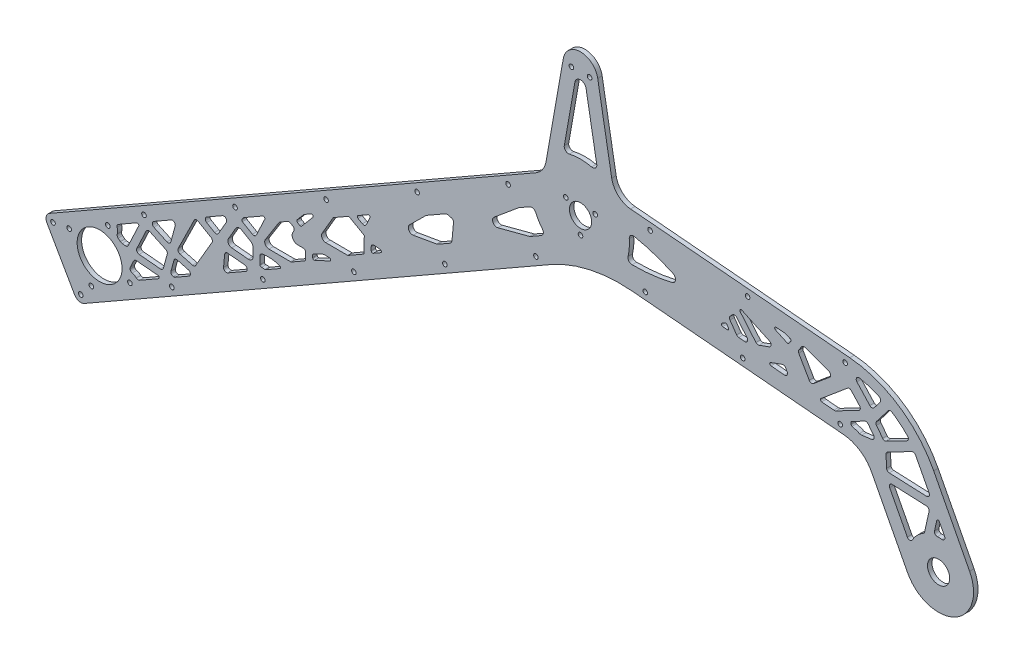
SolidWorks part; units mm, degrees
material "6061-T6 (SS)"
ref_plane "Front Plane" through (0, 0, 0) normal (0, 0, 1) x (1, 0, 0)
ref_plane "Top Plane" through (0, 0, 0) normal (0, 1, 0) x (1, 0, 0)
ref_plane "Right Plane" through (0, 0, 0) normal (1, 0, 0) x (0, 0, -1)
sketch "Reference Sketch" plane through (0, 0, 0) normal (0, 0, 1) x (1, 0, 0)
  line L0 (-343.92, -196.825) -> (0, 0) construction
  line L1 (-243.92, 103.175) -> (356.08, 103.175) construction
  line L2 (-243.92, 103.175) -> (-243.92, 0) construction
  line L3 (-243.92, 0) -> (356.08, 0) construction
  line L4 (356.08, 103.175) -> (356.08, 0) construction
  line L5 (0, 0) -> (256.08, -92.7116) construction
  line L6 (256.08, -92.7116) -> (56.08, -196.825) construction
  line L7 (256.08, -92.7116) -> (456.08, -196.825) construction
  line L8 (-343.92, -196.825) -> (56.08, -196.825) construction
  line L9 (56.08, -196.825) -> (456.08, -196.825) construction
  circle A1 centre (-343.92, -196.825) radius 100 construction
  circle A2 centre (56.08, -196.825) radius 100 construction
  circle A3 centre (456.08, -196.825) radius 100 construction
  circle A4 centre (-343.92, -196.825) radius 16.05 construction
  circle A5 centre (-343.92, -196.825) radius 28.55 construction
  circle A6 centre (-343.92, -196.825) radius 38.55 construction
  circle A7 centre (-343.92, -196.825) radius 33.55 construction
  point P13 (-343.92, -296.825)
  point P14 (556.08, -196.825)
  point P17 (-443.92, -196.825)
  dimension "D3" = 32.1
  dimension "D5" = 200
  dimension "D9" = 57.1
  dimension "D10" = 10
  dimension "D11" = 5
  dimension "D1" = 600
  dimension "D2" = 103.175
  dimension "D4" = 243.92
  dimension "D6" = 125
  dimension "D7" = 400
  dimension "D8" = 1000
sketch "Sketch2" plane through (0, 0, 0) normal (0, 0, 1) x (1, 0, 0)
  line L0 (-379.7168, -188.5069) -> (-32.0065, 10.4873)
  line L1 (-354.8814, -231.9028) -> (-21.5627, -41.1449)
  line L2 (-343.92, -196.825) -> (0, 0) construction
  line L3 (-184.3777, -76.7146) -> (-159.5423, -120.1104) construction
  line L4 (-24.685, 20.9013) -> (-12.3101, 91.0831)
  line L5 (12.3101, 91.0831) -> (22.322, 34.3028)
  line L6 (0, 98.4125) -> (0, 112.7) construction
  line L7 (-5.4848, 79.4125) -> (5.4848, 79.4125) construction
  line L8 (5.4848, 79.4125) -> (10.9697, 88.9125) construction
  line L9 (10.9697, 88.9125) -> (5.4848, 98.4125) construction
  line L10 (5.4848, 98.4125) -> (-5.4848, 98.4125) construction
  line L11 (-5.4848, 98.4125) -> (-10.9697, 88.9125) construction
  line L12 (-10.9697, 88.9125) -> (-5.4848, 79.4125) construction
  line L13 (-243.92, 103.175) -> (356.08, 103.175) construction
  line L14 (0, 88.9125) -> (0, 0) construction
  line L15 (35.7868, 21.9646) -> (192.5861, 8.2464)
  line L16 (252.5753, -31.8371) -> (278.2553, -81.1679)
  line L17 (233.9047, -104.2553) -> (208.2247, -54.9245)
  line L18 (36.8237, -28.3172) -> (188.2284, -41.5633)
  line L19 (0, 0) -> (192.5861, -16.8491) construction
  line L21 (-365.6311, -190.9191) -> (-338.0141, -175.1139) construction
  line L22 (-381.5729, -195.33) -> (-361.7045, -230.0467)
  line L23 (256.08, -92.7116) -> (56.08, -196.825) construction
  line L25 (-243.92, 0) -> (356.08, 0) construction
  circle A0 centre (0, 0) radius 7.9375
  circle A1 centre (-343.92, -196.825) radius 16.05
  arc A3 (-12.3101, 91.0831) -> (12.3101, 91.0831) centre (0, 88.9125) cw
  circle A4 centre (0, 88.9125) radius 6.5 construction
  circle A5 centre (-6.5, 88.9125) radius 1.65
  circle A6 centre (6.5, 88.9125) radius 1.65
  circle A7 centre (0, 88.9125) radius 9.5 construction
  arc A8 (252.5753, -31.8371) -> (192.5861, 8.2464) centre (186.0495, -66.4682) ccw
  circle A9 centre (256.08, -92.7116) radius 7.9375
  arc A10 (278.2553, -81.1679) -> (233.9047, -104.2553) centre (256.08, -92.7116) cw
  arc A11 (-21.5627, -41.1449) -> (36.8237, -28.3172) centre (28.1082, -127.9366) cw
  arc A12 (188.2284, -41.5633) -> (208.2247, -54.9245) centre (186.0495, -66.4682) cw
  arc A13 (22.322, 34.3028) -> (35.7868, 21.9646) centre (37.0941, 36.9075) ccw
  arc A14 (-32.0065, 10.4873) -> (-24.685, 20.9013) centre (-39.4572, 23.506) ccw
  circle A17 centre (-343.92, -196.825) radius 22.5 construction
  circle A18 centre (-365.6311, -190.9191) radius 1.65
  circle A19 centre (-338.0141, -175.1139) radius 1.65
  circle A20 centre (-322.2089, -202.7309) radius 1.65
  circle A21 centre (-349.8259, -218.5361) radius 1.65
  arc A27 (-379.7168, -188.5069) -> (-381.5729, -195.33) centre (-377.2333, -192.8465) ccw
  arc A28 (-361.7045, -230.0467) -> (-354.8814, -231.9028) centre (-357.3649, -227.5632) ccw
  circle A29 centre (-343.92, -196.825) radius 33.55 construction
  circle A32 centre (-343.92, -196.825) radius 38.55 construction
  point P16 (-171.96, -98.4125)
  point P64 (-343.92, -196.825)
  dimension "D1" = 15.875
  dimension "D2" = 32.1
  dimension "D3" = 45
  dimension "D5" = 13
  dimension "D6" = 3.3
  dimension "D7" = 6
  dimension "D12" = 50
  dimension "D14" = 100
  dimension "D16" = 15
  dimension "D17" = 5
  dimension "D18" = 25
  dimension "D19" = 3.3
  dimension "D15" = 4
  dimension "D4" = 50
  dimension "D8" = 19
  dimension "D9" = 14.2875
  dimension "D10" = 9.525
  dimension "D11" = 10
  dimension "D13" = 50
extrude "Base" add sketch "Sketch2" along normal blind 3.175
sketch "Sketch3" plane through (0, 0, 3.175) normal (0, 0, 1) x (1, 0, 0)
  line L0 (-343.92, -196.825) -> (0, 0) construction
  line L5 (0, 0) -> (197.3986, -17.2701) construction
  line L6 (192.5861, 8.2464) -> (35.7868, 21.9646) construction
  line L9 (36.8237, -28.3172) -> (188.2284, -41.5633) construction
  line L10 (-31.8958, -41.2976) -> (0, 0) construction
  line L11 (0, 0) -> (46.2693, -24.1244) construction
  circle A0 centre (-357.3649, -227.5632) radius 1.65
  circle A1 centre (-343.92, -196.825) radius 33.55 construction
  arc A2 (-361.7045, -230.0467) -> (-354.8814, -231.9028) centre (-357.3649, -227.5632) ccw construction
  circle A3 centre (-292.2711, -190.3101) radius 1.65
  circle A4 centre (-227.1773, -153.057) radius 1.65
  circle A5 centre (-162.0835, -115.8038) radius 1.65
  circle A6 centre (-96.9897, -78.5507) radius 1.65
  circle A7 centre (-31.8958, -41.2976) radius 1.65
  circle A8 centre (-312.1394, -155.5934) radius 1.65
  circle A9 centre (-377.2333, -192.8465) radius 1.65
  circle A10 centre (-247.0456, -118.3403) radius 1.65
  circle A11 centre (-181.9518, -81.0871) radius 1.65
  circle A12 centre (-116.858, -43.834) radius 1.65
  circle A13 centre (-51.7642, -6.5809) radius 1.65
  circle A14 centre (46.2693, -24.1244) radius 1.65
  circle A15 centre (116.0029, -30.2253) radius 1.65
  circle A16 centre (185.7366, -36.3262) radius 1.65
  circle A17 centre (189.2228, 3.5215) radius 1.65
  circle A18 centre (119.4892, 9.6224) radius 1.65
  circle A19 centre (49.7555, 15.7234) radius 1.65
  dimension "D1" = 3.3
  dimension "D2" = 6
  dimension "D3" = 5
  dimension "D5" = 3
  dimension "D4" = 75
  dimension "D6" = 70
extrude "Strut Holes" cut sketch "Sketch3" against normal through all
sketch "Sketch6" plane through (0, 0, 3.175) normal (0, 0, 1) x (1, 0, 0)
  line L0 (-315.2692, -197.7109) -> (-301.7593, -189.9792)
  line L1 (-354.8814, -231.9028) -> (-21.5627, -41.1449) construction
  line L2 (-289.845, -183.1607) -> (-279.9388, -177.4914)
  line L3 (-225.0683, -146.089) -> (-215.0659, -140.3647)
  line L4 (-202.4189, -105.5114) -> (-200.6862, -106.5205)
  line L5 (-330.4255, -170.6672) -> (-317.3783, -163.2003)
  line L6 (-32.0065, 10.4873) -> (-379.7168, -188.5069) construction
  line L7 (-315.9769, -164.4942) -> (-323.4022, -180.2613)
  line L8 (-325.3934, -181.4009) -> (-327.8261, -181.1787)
  line L9 (-302.165, -188.1154) -> (-317.5291, -186.7124)
  line L10 (-319.5204, -187.852) -> (-321.9207, -192.9489)
  line L11 (-295.5333, -171.6316) -> (-298.2962, -181.7883)
  line L12 (-300.4079, -183.2551) -> (-315.6625, -181.8621)
  line L13 (-317.2901, -179.0183) -> (-310.6415, -164.9005)
  line L14 (-307.9799, -163.9432) -> (-296.6111, -169.2972)
  line L15 (-280.4073, -173.8257) -> (-288.2923, -171.6808)
  line L16 (-290.7472, -173.0857) -> (-292.8686, -180.8843)
  line L17 (-292.7787, -149.122) -> (-305.2156, -156.2396)
  line L18 (-305.0743, -159.7848) -> (-295.766, -164.1685)
  line L19 (-292.984, -162.8841) -> (-289.8554, -151.3828)
  line L20 (-286.4122, -167.0105) -> (-277.4777, -169.4409)
  line L21 (-275.2245, -168.5176) -> (-263.487, -148.3649)
  line L22 (-264.2087, -145.6301) -> (-273.4911, -140.2238)
  line L23 (-276.2919, -141.0684) -> (-287.6814, -164.1971)
  line L24 (-267.3269, -134.556) -> (-255.9817, -128.0631)
  line L25 (-253.26, -130.8055) -> (-258.9575, -140.5878)
  line L26 (-261.6923, -141.3094) -> (-267.3401, -138.02)
  line L27 (-255.2613, -159.7424) -> (-254.4886, -151.2802)
  line L28 (-252.315, -149.4703) -> (-240.2297, -150.5739)
  line L29 (-292.2711, -190.3101) -> (-299.0066, -188.4038) construction
  line L30 (-252.2762, -161.6601) -> (-239.4181, -154.3014)
  line L31 (-246.5402, -131.1894) -> (-251.7948, -140.2114)
  line L32 (-249.4752, -144.7088) -> (-237.508, -145.8016)
  line L33 (-234.2352, -142.8254) -> (-234.2117, -136.6339)
  line L34 (-235.7018, -134.0302) -> (-242.4379, -130.1069)
  line L35 (-229.2226, -139.4963) -> (-229.2439, -145.1246)
  line L36 (-241.7536, -124.7193) -> (-234.6398, -128.8625)
  line L37 (-231.8238, -127.9864) -> (-225.7969, -115.1887)
  line L38 (-227.1983, -113.8948) -> (-240.4869, -121.4998)
  line L39 (-215.6688, -112.1749) -> (-225.38, -127.5855)
  line L40 (-222.8533, -132.1849) -> (-207.4544, -132.2434)
  line L41 (-206.4534, -131.9792) -> (-197.5057, -126.8584)
  line L42 (-196.4991, -125.1302) -> (-196.4845, -121.2849)
  line L43 (-198.4769, -119.2773) -> (-202.2607, -119.2629)
  line L44 (-205.6297, -113.1304) -> (-205.0269, -112.1739)
  line L45 (-205.7124, -109.3794) -> (-207.4618, -108.3605)
  line L46 (-209.4618, -108.3529) -> (-214.9702, -111.5053)
  line L47 (-223.2993, -137.1832) -> (-189.5978, -137.3112) construction
  line L48 (-199.4194, -106.3021) -> (-191.3609, -96.7721)
  line L49 (-192.6212, -95.2585) -> (-197.479, -98.0386)
  line L50 (-198.0128, -98.4831) -> (-202.6792, -104.0016)
  line L51 (-191.4798, -120.0542) -> (-191.4866, -121.8475)
  line L52 (-190.0674, -122.7592) -> (-179.2455, -117.7628)
  line L54 (-190.899, -119.1501) -> (-184.1308, -116.0253)
  line L55 (-183.2849, -115.8411) -> (-179.6609, -115.8549)
  line L56 (-166.4011, -107.9052) -> (-182.2049, -107.8452)
  line L57 (-184.7858, -103.3353) -> (-176.832, -89.6789)
  line L58 (-176.832, -89.6789) -> (-165.639, -83.2731)
  line L59 (-165.639, -83.2731) -> (-154.6405, -89.6789)
  line L60 (-154.6405, -89.6789) -> (-154.6842, -101.1996)
  line L61 (-154.6842, -101.1996) -> (-166.4011, -107.9052)
  line L62 (-176.832, -89.6789) -> (-166.4011, -107.9052) construction
  line L63 (-149.6667, -96.5998) -> (-149.6576, -94.1811)
  line L64 (-147.4757, -92.197) -> (-143.2847, -92.5797)
  line L65 (-142.8789, -94.4434) -> (-148.17, -97.4715)
  line L66 (-159.1247, -79.5451) -> (-152.014, -75.4756)
  line L67 (-150.6126, -76.7696) -> (-153.1821, -82.2258)
  line L68 (-155.9981, -83.102) -> (-159.1313, -81.2771)
  line L69 (-154.1121, -84.2004) -> (-149.6493, -91.9985) construction
  line L70 (-90.8199, -49.6985) -> (-91.8964, -61.4879)
  line L71 (-93.3939, -63.8188) -> (-101.9943, -68.7409)
  line L72 (-102.9747, -69.0935) -> (-119.6299, -71.9651)
  line L73 (-122.2529, -66.8794) -> (-110.6811, -55.3952)
  line L74 (-110.058, -54.9208) -> (-96.7247, -47.2901)
  line L75 (-94.4471, -46.9991) -> (-92.2866, -47.5868)
  line L76 (-102.4534, -69.0036) -> (-110.4008, -55.117) construction
  line L78 (-28.0968, -26.4494) -> (-35.8254, -30.8725)
  line L79 (-36.5501, -31.1694) -> (-59.134, -37.129)
  line L80 (-61.819, -31.9228) -> (-44.3172, -17.3499)
  line L81 (-43.8877, -17.0516) -> (-36.2746, -12.6946)
  line L82 (-44.1155, -17.182) -> (-36.1682, -31.0687) construction
  line L83 (-11.5997, 37.5245) -> (-3.9861, 80.7029)
  line L84 (3.9861, 80.7029) -> (11.5997, 37.5245)
  line L85 (22.322, 34.3028) -> (12.3101, 91.0831) construction
  line L86 (-12.3101, 91.0831) -> (-24.685, 20.9013) construction
  line L87 (192.5861, 8.2464) -> (35.7868, 21.9646) construction
  line L88 (36.8237, -28.3172) -> (188.2284, -41.5633) construction
  line L89 (-227.1773, -153.057) -> (-233.9128, -151.1507) construction
  line L90 (246.076, -72.9136) -> (249.254, -58.5784)
  line L91 (247.3887, -56.1475) -> (222.9622, -55.081)
  line L92 (221.1009, -58.0026) -> (233.7353, -82.273)
  line L93 (208.2247, -54.9245) -> (233.9047, -104.2553) construction
  line L94 (253.1337, -68.7997) -> (254.752, -61.5)
  line L95 (256.6153, -61.2547) -> (260.3456, -68.4206)
  line L96 (278.2553, -81.1679) -> (252.5753, -31.8371) construction
  line L97 (249.3108, -47.2228) -> (239.5975, -28.5637)
  line L98 (236.9, -27.7132) -> (219.5656, -36.7369)
  line L99 (218.491, -38.5982) -> (218.8608, -47.0688)
  line L100 (220.7717, -48.9796) -> (247.4495, -50.1444)
  line L101 (233.4135, -22.7639) -> (218.6181, -30.4658)
  line L102 (216.1079, -29.9093) -> (211.6718, -24.1281)
  line L103 (211.6718, -21.693) -> (220.0072, -10.8302)
  line L104 (209.6166, -31.3057) -> (205.7463, -26.2618)
  line L105 (203.2361, -25.7053) -> (194.0101, -30.5081)
  line L106 (193.4718, -31.3951) -> (193.4718, -32.4967)
  line L107 (201.069, -35.4569) -> (208.2909, -34.5061)
  line L108 (214.3031, -8.4078) -> (209.9577, -14.0708)
  line L109 (197.6887, -4.156) -> (206.8964, -14.2045)
  line L110 (193.6814, -11.6243) -> (199.5455, -18.0239)
  line L111 (198.9945, -21.1491) -> (182.8075, -29.5754)
  line L112 (181.1608, -29.903) -> (172.4826, -29.1438)
  line L113 (171.927, -27.3815) -> (190.9213, -11.4434)
  line L114 (178.1992, -11.0225) -> (166.5918, -20.7623)
  line L115 (163.5742, -20.2302) -> (156.048, -7.1944)
  line L116 (156.1417, -5.0472) -> (158.1885, -2.1242)
  line L117 (160.5108, -1.3919) -> (177.5977, -7.611)
  line L118 (146.6448, -20.9077) -> (147.747, -22.8167)
  line L119 (145.8406, -25.8091) -> (136.23, -24.9682)
  line L120 (135.9751, -23.0324) -> (144.2287, -20.0283)
  line L121 (134.9743, -13.819) -> (127.6718, -16.4769)
  line L122 (125.4557, -15.8831) -> (114.1985, -2.4673)
  line L123 (115.3872, -0.9182) -> (135.1355, -10.127)
  line L124 (139.4306, -1.096) -> (147.8318, -5.0136)
  line L125 (149.0736, -4.6809) -> (150.4259, -2.7496)
  line L126 (149.9488, -1.2363) -> (146.0985, 0.1651)
  line L127 (145.3339, 0.3346) -> (139.9404, 0.8065)
  line L128 (111.6605, -7.2212) -> (119.0455, -16.0223)
  line L129 (117.3391, -19.3002) -> (113.1162, -18.9308)
  line L130 (111.6522, -18.0855) -> (106.8775, -11.2665)
  line L131 (107.1016, -8.7052) -> (108.7142, -7.0926)
  line L132 (104.7039, -15.1361) -> (105.7554, -16.6377)
  line L133 (104.8491, -18.2075) -> (101.6773, -17.93)
  line L134 (101.2644, -16.0678) -> (103.3847, -14.8436)
  arc A0 (-317.584, -197.4764) -> (-320.5599, -195.9279) centre (-322.2089, -202.7309) ccw
  arc A1 (-291.1568, -183.3993) -> (-291.2348, -183.3872) centre (-292.2711, -190.3101) ccw
  arc A2 (-225.7665, -146.2006) -> (-228.1106, -146.1195) centre (-227.1773, -153.057) ccw
  arc A4 (-322.0747, -194.2209) -> (-322.0953, -194.053) centre (-343.92, -196.825) ccw
  arc A5 (-331.3132, -177.1382) -> (-331.3392, -173.0054) centre (-338.0141, -175.1139) ccw
  arc A6 (-329.0005, -180.6569) -> (-330.6088, -179.309) centre (-343.92, -196.825) ccw
  arc A8 (-227.5555, -137.5318) -> (-215.2363, -138.5515) centre (-223.3943, -162.1831) cw
  arc A9 (-241.9747, -123.1658) -> (-241.1717, -122.1478) centre (-247.0456, -118.3403) ccw
  arc A10 (-32.0383, -14.0906) -> (-27.2511, -21.9631) centre (0, 0) ccw
  arc A11 (-251.7948, -140.2114) -> (-249.4752, -144.7088) centre (-249.2024, -141.7213) ccw
  arc A12 (-225.38, -127.5855) -> (-222.8533, -132.1849) centre (-222.8419, -129.1849) ccw
  arc A13 (-182.2049, -107.8452) -> (-184.7858, -103.3353) centre (-182.1935, -104.8452) cw
  arc A14 (-119.6299, -71.9651) -> (-122.2529, -66.8794) centre (-120.1396, -69.0087) cw
  arc A15 (-59.134, -37.129) -> (-61.819, -31.9228) centre (-59.8994, -34.2283) cw
  arc A16 (-7.9627, 34.0822) -> (7.9627, 34.0822) centre (0, 0) cw
  arc A17 (-3.9861, 80.7029) -> (3.9861, 80.7029) centre (0, 80) cw
  arc A18 (34.8636, 3.0867) -> (34.0029, -8.2948) centre (0, 0) cw
  arc A19 (38.4335, 6.2944) -> (66.0977, -2.7713) centre (15.1723, -111.4295) cw
  arc A20 (66.0977, -2.7713) -> (65.4856, -8.7407) centre (64.749, -5.6491) cw
  arc A21 (36.898, -12.0057) -> (65.4856, -8.7407) centre (37.6733, 107.9918) ccw
  arc A22 (245.141, -74.2025) -> (237.26, -82.3165) centre (256.08, -92.7116) ccw
  arc A23 (258.3595, -71.3328) -> (255.1708, -71.2308) centre (256.08, -92.7116) ccw
  arc A24 (222.6875, -10.3732) -> (233.9189, -19.5905) centre (186.0495, -66.4682) cw
  arc A25 (252.5753, -31.8371) -> (192.5861, 8.2464) centre (186.0495, -66.4682) ccw construction
  arc A26 (194.2312, -33.4673) -> (199.4914, -35.2382) centre (186.0495, -66.4682) cw
  arc A27 (208.2247, -54.9245) -> (188.2284, -41.5633) centre (186.0495, -66.4682) ccw construction
  arc A28 (213.5369, -5.3663) -> (199.5667, -0.8459) centre (186.0495, -66.4682) ccw
  arc A29 (218.8608, -47.0688) -> (220.7717, -48.9796) centre (220.8589, -46.9815) ccw
  arc A30 (239.5975, -28.5637) -> (236.9, -27.7132) centre (237.8235, -29.4872) ccw
  arc A31 (219.5656, -36.7369) -> (218.491, -38.5982) centre (220.4891, -38.5109) ccw
  arc A32 (127.6718, -16.4769) -> (125.4557, -15.8831) centre (126.9878, -14.5975) cw
  arc A33 (-240.4869, -121.4998) -> (-241.1717, -122.1478) centre (-239.4934, -123.2356) ccw
  arc A34 (-234.6398, -128.8625) -> (-231.8238, -127.9864) centre (-233.6332, -127.1343) ccw
  arc A35 (-229.2226, -139.4963) -> (-227.5555, -137.5318) centre (-227.2226, -139.5039) cw
  arc A36 (-315.2692, -197.7109) -> (-317.584, -197.4764) centre (-316.2626, -195.9751) cw
  arc A37 (-322.0747, -194.2209) -> (-320.5599, -195.9279) centre (-320.0887, -193.9842) ccw
  arc A38 (-321.9207, -192.9489) -> (-322.0953, -194.053) centre (-320.1113, -193.801) ccw
  arc A39 (-317.5291, -186.7124) -> (-319.5204, -187.852) centre (-317.711, -188.7042) ccw
  arc A40 (-323.4022, -180.2613) -> (-325.3934, -181.4009) centre (-325.2116, -179.4092) cw
  arc A41 (-327.8261, -181.1787) -> (-329.0005, -180.6569) centre (-327.6442, -179.187) cw
  arc A42 (-331.3132, -177.1382) -> (-330.6088, -179.309) centre (-329.3986, -177.7166) ccw
  arc A43 (-330.4255, -170.6672) -> (-331.3392, -173.0054) centre (-329.4321, -172.403) ccw
  arc A44 (-315.6625, -181.8621) -> (-317.2901, -179.0183) centre (-315.4807, -179.8704) cw
  arc A45 (-298.2962, -181.7883) -> (-300.4079, -183.2551) centre (-300.226, -181.2634) cw
  arc A46 (-289.845, -183.1607) -> (-291.1568, -183.3993) centre (-290.8384, -181.4248) cw
  arc A47 (-292.8686, -180.8843) -> (-291.2348, -183.3872) centre (-290.9387, -181.4092) ccw
  arc A48 (-280.4073, -173.8257) -> (-279.9388, -177.4914) centre (-280.9322, -175.7556) cw
  arc A49 (-288.2923, -171.6808) -> (-290.7472, -173.0857) centre (-288.8173, -173.6107) ccw
  arc A50 (-295.5333, -171.6316) -> (-296.6111, -169.2972) centre (-297.4632, -171.1066) ccw
  arc A51 (-310.6415, -164.9005) -> (-307.9799, -163.9432) centre (-308.8321, -165.7526) cw
  arc A52 (-305.2156, -156.2396) -> (-305.0743, -159.7848) centre (-304.2222, -157.9754) ccw
  arc A53 (-292.7787, -149.122) -> (-289.8554, -151.3828) centre (-291.7853, -150.8578) cw
  arc A54 (-295.766, -164.1685) -> (-292.984, -162.8841) centre (-294.9139, -162.3591) ccw
  arc A55 (-286.4122, -167.0105) -> (-287.6814, -164.1971) centre (-285.8872, -165.0807) cw
  arc A56 (-277.4777, -169.4409) -> (-275.2245, -168.5176) centre (-276.9527, -167.511) ccw
  arc A57 (-263.487, -148.3649) -> (-264.2087, -145.6301) centre (-265.2153, -147.3583) ccw
  arc A58 (-273.4911, -140.2238) -> (-276.2919, -141.0684) centre (-274.4977, -141.952) ccw
  arc A59 (-267.3269, -134.556) -> (-267.3401, -138.02) centre (-266.3335, -136.2918) ccw
  arc A60 (-258.9575, -140.5878) -> (-261.6923, -141.3094) centre (-260.6857, -139.5812) cw
  arc A61 (-254.4886, -151.2802) -> (-252.315, -149.4703) centre (-252.4969, -151.462) cw
  arc A62 (-255.2613, -159.7424) -> (-252.2762, -161.6601) centre (-253.2696, -159.9243) ccw
  arc A63 (-239.4181, -154.3014) -> (-240.2297, -150.5739) centre (-240.4115, -152.5656) ccw
  arc A64 (-255.9817, -128.0631) -> (-253.26, -130.8055) centre (-254.9883, -129.7989) cw
  arc A65 (-207.4544, -132.2434) -> (-206.4534, -131.9792) centre (-207.4468, -130.2434) ccw
  arc A66 (-214.9702, -111.5053) -> (-215.6688, -112.1749) centre (-213.9767, -113.2412) ccw
  arc A67 (-207.4618, -108.3605) -> (-209.4618, -108.3529) centre (-208.4684, -110.0887) ccw
  arc A68 (-205.0269, -112.1739) -> (-205.7124, -109.3794) centre (-206.719, -111.1076) ccw
  arc A69 (-202.2607, -119.2629) -> (-205.6297, -113.1304) centre (-202.2456, -115.263) cw
  arc A70 (-196.4845, -121.2849) -> (-198.4769, -119.2773) centre (-198.4845, -121.2773) ccw
  arc A71 (-197.5057, -126.8584) -> (-196.4991, -125.1302) centre (-198.4991, -125.1226) ccw
  arc A72 (-184.1308, -116.0253) -> (-183.2849, -115.8411) centre (-183.2925, -117.8411) cw
  arc A73 (-197.479, -98.0386) -> (-198.0128, -98.4831) centre (-196.4856, -99.7744) ccw
  arc A74 (-149.6576, -94.1811) -> (-147.4757, -92.197) centre (-147.6576, -94.1887) cw
  arc A75 (-153.1821, -82.2258) -> (-155.9981, -83.102) centre (-154.9915, -81.3737) cw
  arc A76 (-90.8199, -49.6985) -> (-92.2866, -47.5868) centre (-92.8116, -49.5167) ccw
  arc A77 (111.6605, -7.2212) -> (108.7142, -7.0926) centre (110.1284, -8.5068) ccw
  arc A78 (106.8775, -11.2665) -> (107.1016, -8.7052) centre (108.5158, -10.1194) cw
  arc A79 (113.1162, -18.9308) -> (111.6522, -18.0855) centre (113.2905, -16.9384) cw
  arc A80 (119.0455, -16.0223) -> (117.3391, -19.3002) centre (117.5134, -17.3078) cw
  arc A81 (134.9743, -13.819) -> (135.1355, -10.127) centre (134.2903, -11.9396) ccw
  arc A82 (146.6448, -20.9077) -> (144.2287, -20.0283) centre (144.9128, -21.9077) ccw
  arc A83 (147.747, -22.8167) -> (145.8406, -25.8091) centre (146.0149, -23.8167) cw
  arc A84 (156.048, -7.1944) -> (156.1417, -5.0472) centre (157.78, -6.1944) cw
  arc A85 (158.1885, -2.1242) -> (160.5108, -1.3919) centre (159.8268, -3.2713) cw
  arc A86 (178.1992, -11.0225) -> (177.5977, -7.611) centre (176.9136, -9.4904) ccw
  arc A87 (166.5918, -20.7623) -> (163.5742, -20.2302) centre (165.3062, -19.2302) cw
  arc A88 (193.6814, -11.6243) -> (190.9213, -11.4434) centre (192.2068, -12.9755) ccw
  arc A89 (199.5455, -18.0239) -> (198.9945, -21.1491) centre (198.071, -19.375) cw
  arc A90 (209.9577, -14.0708) -> (206.8964, -14.2045) centre (208.371, -12.8533) cw
  arc A91 (213.5369, -5.3663) -> (214.3031, -8.4078) centre (212.7164, -7.1903) cw
  arc A92 (233.9189, -19.5905) -> (233.4135, -22.7639) centre (232.49, -20.9899) cw
  arc A93 (222.6875, -10.3732) -> (220.0072, -10.8302) centre (221.5939, -12.0477) ccw
  arc A94 (211.6718, -24.1281) -> (211.6718, -21.693) centre (213.2585, -22.9105) cw
  arc A95 (218.6181, -30.4658) -> (216.1079, -29.9093) centre (217.6946, -28.6918) cw
  arc A96 (205.7463, -26.2618) -> (203.2361, -25.7053) centre (204.1595, -27.4793) ccw
  arc A97 (209.6166, -31.3057) -> (208.2909, -34.5061) centre (208.0299, -32.5232) cw
  arc A98 (246.076, -72.9136) -> (245.141, -74.2025) centre (244.1234, -72.4807) cw
  arc A99 (249.254, -58.5784) -> (247.3887, -56.1475) centre (247.3014, -58.1456) ccw
  arc A100 (222.9622, -55.081) -> (221.1009, -58.0026) centre (222.8749, -57.0791) ccw
  arc A101 (233.7353, -82.273) -> (237.26, -82.3165) centre (235.5093, -81.3495) ccw
  arc A102 (260.3456, -68.4206) -> (258.3595, -71.3328) centre (258.5716, -69.344) cw
  arc A103 (253.1337, -68.7997) -> (255.1708, -71.2308) centre (255.0863, -69.2326) ccw
  arc A104 (249.3108, -47.2228) -> (247.4495, -50.1444) centre (247.5367, -48.1463) cw
  arc A105 (199.5667, -0.8459) -> (197.6887, -4.156) centre (199.1632, -2.8048) ccw
  arc A106 (-215.2363, -138.5515) -> (-215.0659, -140.3647) centre (-215.5626, -139.4968) cw
  arc A107 (-301.7593, -189.9792) -> (-302.165, -188.1154) centre (-302.256, -189.1113) ccw
  arc A108 (-317.3783, -163.2003) -> (-315.9769, -164.4942) centre (-316.8815, -164.0682) cw
  arc A109 (-225.7969, -115.1887) -> (-227.1983, -113.8948) centre (-226.7016, -114.7627) ccw
  arc A110 (-241.7536, -124.7193) -> (-241.9747, -123.1658) centre (-241.2503, -123.8551) cw
  arc A111 (-225.7665, -146.2006) -> (-225.0683, -146.089) centre (-225.565, -145.2211) ccw
  arc A112 (-229.2439, -145.1246) -> (-228.1106, -146.1195) centre (-228.2439, -145.1284) ccw
  arc A113 (-202.4189, -105.5114) -> (-202.6792, -104.0016) centre (-201.9156, -104.6473) cw
  arc A114 (-200.6862, -106.5205) -> (-199.4194, -106.3021) centre (-200.183, -105.6564) ccw
  arc A115 (-191.4798, -120.0542) -> (-190.899, -119.1501) centre (-190.4798, -120.058) cw
  arc A116 (-191.4866, -121.8475) -> (-190.0674, -122.7592) centre (-190.4866, -121.8513) ccw
  arc A117 (-191.3609, -96.7721) -> (-192.6212, -95.2585) centre (-192.1245, -96.1264) ccw
  arc A118 (-179.2455, -117.7628) -> (-179.6609, -115.8549) centre (-179.6647, -116.8549) ccw
  arc A119 (-152.014, -75.4756) -> (-150.6126, -76.7696) centre (-151.5173, -76.3435) cw
  arc A120 (-159.1247, -79.5451) -> (-159.1313, -81.2771) centre (-158.628, -80.413) ccw
  arc A121 (-149.6667, -96.5998) -> (-148.17, -97.4715) centre (-148.6667, -96.6036) ccw
  arc A122 (-143.2847, -92.5797) -> (-142.8789, -94.4434) centre (-143.3756, -93.5755) cw
  arc A123 (101.6773, -17.93) -> (101.2644, -16.0678) centre (101.7644, -16.9338) cw
  arc A124 (104.7039, -15.1361) -> (103.3847, -14.8436) centre (103.8847, -15.7096) ccw
  arc A125 (105.7554, -16.6377) -> (104.8491, -18.2075) centre (104.9362, -17.2113) cw
  arc A126 (114.1985, -2.4673) -> (115.3872, -0.9182) centre (114.9646, -1.8245) cw
  arc A127 (136.23, -24.9682) -> (135.9751, -23.0324) centre (136.3171, -23.972) cw
  arc A128 (139.4306, -1.096) -> (139.9404, 0.8065) centre (139.8532, -0.1897) cw
  arc A129 (172.4826, -29.1438) -> (171.927, -27.3815) centre (172.5698, -28.1476) cw
  arc A130 (194.0101, -30.5081) -> (193.4718, -31.3951) centre (194.4718, -31.3951) ccw
  arc A131 (193.4718, -32.4967) -> (194.2312, -33.4673) centre (194.4718, -32.4967) ccw
  arc A132 (254.752, -61.5) -> (256.6153, -61.2547) centre (255.7283, -61.7164) cw
  arc A133 (146.0985, 0.1651) -> (145.3339, 0.3346) centre (145.0724, -2.654) ccw
  arc A134 (199.4914, -35.2382) -> (201.069, -35.4569) centre (200.6774, -32.4826) ccw
  arc A135 (182.8075, -29.5754) -> (181.1608, -29.903) centre (181.4223, -26.9144) cw
  arc A136 (-7.9627, 34.0822) -> (-11.5997, 37.5245) centre (-8.6452, 37.0035) cw
  arc A137 (7.9627, 34.0822) -> (11.5997, 37.5245) centre (8.6452, 37.0035) ccw
  arc A138 (34.8636, 3.0867) -> (38.4335, 6.2944) centre (37.8519, 3.3513) cw
  arc A139 (34.0029, -8.2948) -> (36.898, -12.0057) centre (36.9174, -9.0058) ccw
  arc A140 (-35.8254, -30.8725) -> (-36.5501, -31.1694) centre (-37.3155, -28.2687) cw
  arc A141 (-44.3172, -17.3499) -> (-43.8877, -17.0516) centre (-42.3976, -19.6554) cw
  arc A142 (-32.0383, -14.0906) -> (-36.2746, -12.6946) centre (-34.7845, -15.2984) ccw
  arc A143 (-27.2511, -21.9631) -> (-28.0968, -26.4494) centre (-29.5869, -23.8456) cw
  arc A144 (-96.7247, -47.2901) -> (-94.4471, -46.9991) centre (-95.2346, -49.8939) cw
  arc A145 (-91.8964, -61.4879) -> (-93.3939, -63.8188) centre (-94.884, -61.2151) cw
  arc A146 (-110.6811, -55.3952) -> (-110.058, -54.9208) centre (-108.5679, -57.5245) cw
  arc A147 (-101.9943, -68.7409) -> (-102.9747, -69.0935) centre (-103.4845, -66.1371) cw
  arc A148 (-246.5402, -131.1894) -> (-242.4379, -130.1069) centre (-243.9478, -132.6992) cw
  arc A149 (-234.2117, -136.6339) -> (-235.7018, -134.0302) centre (-237.2117, -136.6225) ccw
  arc A150 (-237.508, -145.8016) -> (-234.2352, -142.8254) centre (-237.2352, -142.8141) ccw
  arc A151 (150.4259, -2.7496) -> (149.9488, -1.2363) centre (149.6067, -2.176) ccw
  arc A152 (147.8318, -5.0136) -> (149.0736, -4.6809) centre (148.2544, -4.1073) ccw
  point P98 (-116.858, -43.834)
  point P110 (-254.1648, -144.2806)
  point P113 (-228.2654, -132.1643)
  point P143 (34.9003, -2.6394)
  point P203 (218.9408, -48.8997)
  point P206 (238.674, -26.7897)
  point P211 (126.3559, -16.9559)
  point P214 (-240.9361, -121.7569)
  point P217 (-232.7537, -129.961)
  point P220 (-229.2164, -137.8704)
  point P229 (-318.9237, -186.5851)
  point P232 (-323.9988, -181.5282)
  point P235 (-328.5183, -181.1155)
  point P240 (-331.9839, -171.5591)
  point P247 (-290.5028, -183.5371)
  point P252 (-275.7482, -175.0931)
  point P255 (-290.2222, -171.1558)
  point P262 (-308.5502, -158.1479)
  point P265 (-288.588, -146.7237)
  point P268 (-293.6097, -165.184)
  point P271 (-288.7533, -166.3737)
  point P278 (-275.3444, -139.1443)
  point P281 (-270.3335, -136.2766)
  point P288 (-255.6107, -163.5684)
  point P294 (-249.5035, -124.3556)
  point P297 (-206.9185, -132.2454)
  point P300 (-215.403, -111.753)
  point P303 (-208.4596, -107.7794)
  point P308 (-209.4769, -119.2355)
  point P311 (-196.4769, -119.2849)
  point P314 (-196.5035, -126.2849)
  point P329 (110.2575, -5.5492)
  point P334 (112.1872, -18.8495)
  point P337 (122.1491, -19.721)
  point P340 (139.5116, -12.1676)
  point P345 (149.6679, -26.1439)
  point P350 (159.0687, -0.8671)
  point P353 (180.8529, -8.7958)
  point P356 (164.7659, -22.2944)
  point P363 (208.5067, -15.9618)
  point P366 (215.8118, -6.4415)
  point P369 (235.7568, -21.544)
  point P374 (210.7376, -22.9105)
  point P377 (217.1296, -31.2407)
  point P380 (204.7246, -24.9304)
  point P383 (211.7254, -34.054)
  point P390 (219.5014, -54.9299)
  point P393 (235.6626, -85.9753)
  point P396 (262.2729, -72.1228)
  point P401 (250.9103, -50.2955)
  point P406 (-213.2581, -139.3301)
  point P412 (-314.6256, -161.6249)
  point P415 (-224.4456, -112.3194)
  point P420 (-225.4089, -146.284)
  point P423 (-229.2487, -146.3704)
  point P426 (-203.4487, -104.9116)
  point P431 (-191.4774, -119.4171)
  point P434 (-191.4925, -123.4171)
  point P437 (-187.699, -92.4415)
  point P440 (-175.1502, -115.872)
  point P447 (-149.6733, -98.3319)
  point P450 (-140.1262, -92.8681)
  point P453 (98.5177, -17.6536)
  point P458 (106.9854, -18.3944)
  point P463 (131.7364, -24.5751)
  point P468 (170.0776, -28.9333)
  point P471 (193.4718, -30.7883)
  point P474 (193.4718, -33.2883)
  point P477 (255.3467, -58.8176)
  point P484 (182.0319, -29.9792)
  point P491 (34.2849, 7.0387)
  point P494 (32.91, -11.9136)
  point P505 (-24.8853, -24.6115)
  point P508 (-95.6462, -46.6729)
  point P511 (-92.0384, -63.0431)
  point P524 (-234.2477, -146.0993)
  point P527 (151.1734, -1.682)
  point P530 (148.5923, -5.3682)
  dimension "D1" = 14
  dimension "D2" = 10
  dimension "D3" = 2
  dimension "D5" = 22
  dimension "D6" = 9
  dimension "D12" = 5
  dimension "D19" = 7
  dimension "D31" = 7
  dimension "D40" = 25
  dimension "D44" = 19
  dimension "D62" = 5
  dimension "D92" = 35
  dimension "D96" = 3
  dimension "D97" = 10
  dimension "D100" = 15
  dimension "D104" = 30
  dimension "D105" = 120
  dimension "D107" = 43
  dimension "D116" = 65
  dimension "D117" = 8
  dimension "D127" = 9
  dimension "D128" = 6
  dimension "D171" = 2
  dimension "D172" = 1
  dimension "D173" = 3
  dimension "D174" = 1
  dimension "D175" = 4
  dimension "D7" = 35
  dimension "D8" = 35
  dimension "D9" = 20
  dimension "D10" = 22
  dimension "D11" = 20
  dimension "D13" = 5
  dimension "D14" = 45
  dimension "D15" = 45
  dimension "D16" = 17
  dimension "D17" = 15
  dimension "D18" = 5
  dimension "D20" = 55
  dimension "D21" = 5
  dimension "D22" = 45
  dimension "D23" = 23
  dimension "D24" = 34
  dimension "D25" = 60
  dimension "D26" = 5
  dimension "D27" = 5
  dimension "D28" = 5
  dimension "D29" = 30
  dimension "D30" = 24
  dimension "D32" = 55
  dimension "D33" = 35
  dimension "D34" = 25
  dimension "D35" = 5
  dimension "D36" = 6
  dimension "D37" = 60
  dimension "D38" = 5
  dimension "D39" = 20
  dimension "D41" = 11
  dimension "D42" = 35
  dimension "D43" = 60
  dimension "D45" = 19.5
  dimension "D46" = 5
  dimension "D47" = 5
  dimension "D48" = 30
  dimension "D49" = 5
  dimension "D50" = 14
  dimension "D51" = 13
  dimension "D52" = 8.5
  dimension "D53" = 60
  dimension "D54" = 12
  dimension "D55" = 7
  dimension "D56" = 22
  dimension "D57" = 28
  dimension "D58" = 60
  dimension "D59" = 15
  dimension "D60" = 8
  dimension "D61" = 13
  dimension "D63" = 12
  dimension "D64" = 20
  dimension "D65" = 5
  dimension "D66" = 65
  dimension "D67" = 25
  dimension "2" = 18
  dimension "D68" = 8
  dimension "D69" = 4
  dimension "D70" = 14
  dimension "D71" = 15
  dimension "D72" = 13.5
  dimension "D73" = 60
  dimension "D74" = 60
  dimension "D75" = 8
  dimension "D76" = 5
  dimension "D77" = 35
  dimension "D78" = 0.5076
  dimension "D79" = 5
  dimension "D80" = 11
  dimension "D81" = 35
  dimension "D82" = 16
  dimension "D83" = 18
  dimension "D84" = 55
  dimension "D85" = 45
  dimension "D86" = 20
  dimension "D87" = 15
  dimension "D88" = 12
  dimension "D89" = 17
  dimension "D90" = 16
  dimension "D91" = 18
  dimension "D93" = 15
  dimension "D94" = 10
  dimension "D95" = 13
  dimension "D98" = 10
  dimension "D99" = 80
  dimension "D101" = 16
  dimension "D102" = 22
  dimension "D103" = 22
  dimension "D106" = 7
  dimension "D108" = 10
  dimension "D109" = 40
  dimension "D110" = 10
  dimension "D111" = 6
  dimension "D112" = 60
  dimension "D113" = 35
  dimension "D114" = 15
  dimension "D115" = 6
  dimension "D118" = 26.5
  dimension "D119" = 6
  dimension "D120" = 85
  dimension "D121" = 85
  dimension "D122" = 32
  dimension "D123" = 21
  dimension "D124" = 80
  dimension "D125" = 75
  dimension "D126" = 6
  dimension "D129" = 10.5
  dimension "D130" = 80
  dimension "D131" = 12
  dimension "D132" = 8
  dimension "D133" = 6
  dimension "D134" = 2.5
  dimension "D135" = 100
  dimension "D136" = 11.5
  dimension "D137" = 60
  dimension "D138" = 11
  dimension "D139" = 45
  dimension "D140" = 12
  dimension "D141" = 8.5
  dimension "D142" = 12
  dimension "D143" = 18
  dimension "D144" = 80
  dimension "D145" = 21
  dimension "D146" = 60
  dimension "D147" = 60
  dimension "D148" = 15
  dimension "D149" = 12
  dimension "D150" = 18
  dimension "D151" = 25
  dimension "D152" = 9
  dimension "D153" = 12
  dimension "D154" = 6
  dimension "D155" = 15
  dimension "D156" = 20
  dimension "D157" = 10
  dimension "D158" = 13.5
  dimension "D159" = 4.5
  dimension "D160" = 45
  dimension "D161" = 14
  dimension "D162" = 5
  dimension "D163" = 10
  dimension "D164" = 16
  dimension "D165" = 50
  dimension "D166" = 18.5
  dimension "D167" = 50
  dimension "D168" = 4
  dimension "D169" = 8.5
  dimension "D170" = 35
extrude "Lightening Holes" cut sketch "Sketch6" against normal through all
sketch "Sketch7" plane through (0, 0, 3.175) normal (0, 0, 1) x (1, 0, 0)
  circle A0 centre (-10.5, 6.0622) radius 1.65
  circle A1 centre (10.5, 6.0622) radius 1.65
  circle A2 centre (0, -12.1244) radius 1.65
  point P8 (0, 0)
  dimension "D1" = 3.3
  dimension "D3" = 21
  dimension "D2" = 3
extrude "Cut-Extrude1" cut sketch "Sketch7" against normal through all
